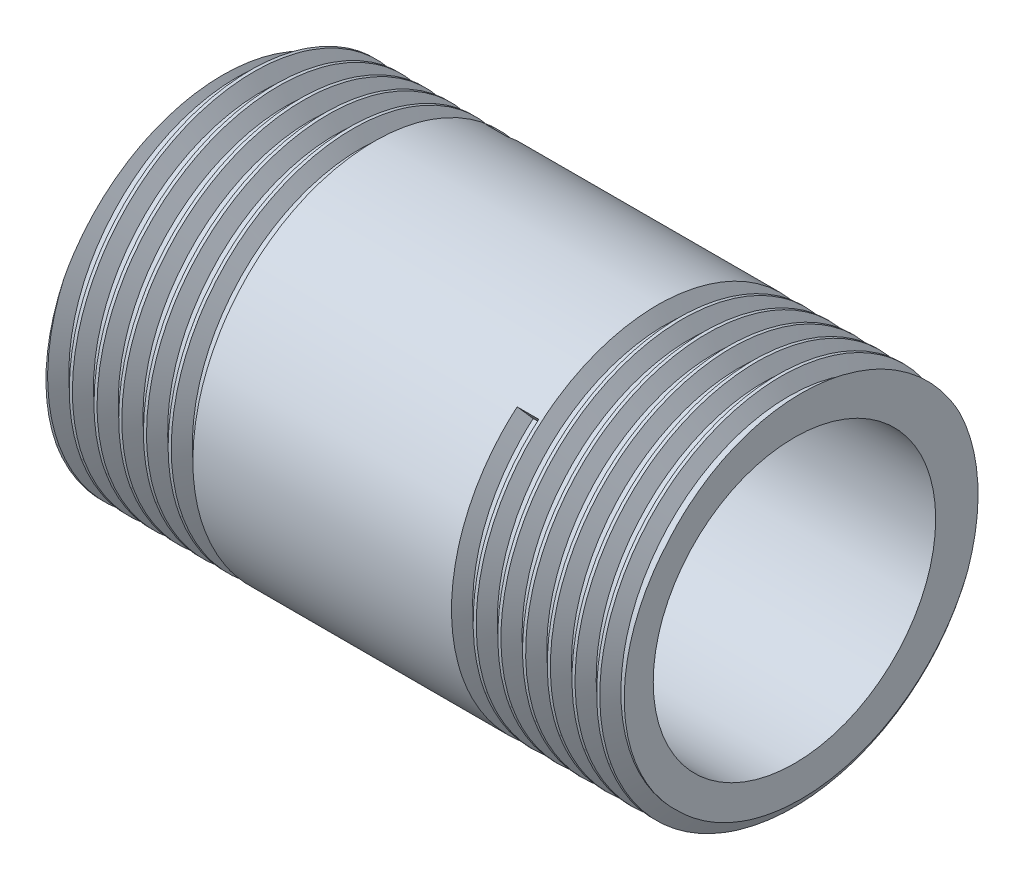
SolidWorks part; units mm, degrees
material "PVC rigide"
ref_plane "Plan de face" through (0, 0, 0) normal (0, 0, 1) x (1, 0, 0)
ref_plane "Plan de dessus" through (0, 0, 0) normal (0, 1, 0) x (1, 0, 0)
ref_plane "Plan de droite" through (0, 0, 0) normal (1, 0, 0) x (0, 0, -1)
sketch "Esquisse2" plane through (0, 0, 0) normal (1, 0, 0) x (0, 0, -1)
  circle A0 centre (0, 0) radius 13
  dimension "D1" = 26
extrude "Boss.-Extru.1" add sketch "Esquisse2" along normal mid plane 45
thread "Filetage1" pitch 1.75 method cut profile "Profil de filetage1" start angle 0, offset 0, length 12.5, pitch 1.75, diameter 26
ref_plane "Plan1" through (-22.5, 0, -13) normal (0, -1, 0) x (0, 0, -1)
sketch "Profil de filetage1" plane through (-22.5, 0, -13) normal (0, -1, 0) x (0, 0, -1)
  line L0 (0, 0) -> (0, 1.75) construction
  line L11 (0, 0) -> (0, 1.5312)
  line L12 (0, 1.5312) -> (-0.9472, 0.9844)
  line L13 (-0.9472, 0.9844) -> (-0.9472, 0.5469)
  line L15 (-0.9472, 0.5469) -> (0, 0)
  line L17 (-0.9472, 0.7656) -> (0, 0.7656) construction
  point P2 (0, 0)
  dimension "Pitch" = 1.75
  dimension "Profile_Angle" = 60
  dimension "Profile_Land" = 0.4375
  dimension "Profile_Height" = 0.9472
sketch "Esquisse5" plane through (-22.5, 0, 0) normal (-1, 0, 0) x (0, 0, 1)
  circle A0 centre (0, 0) radius 13.5
  dimension "D1" = 27
extrude "Enlèv. mat.-Extru.1" cut sketch "Esquisse5" against normal blind 2.5
thread "Filetage2" pitch 1.75 method cut profile "Profil de filetage2" start angle 0, offset 0, length 12.5, pitch 1.75, diameter 26
ref_plane "Plan2" through (22.5, 0, 13) normal (0, -1, 0) x (0, 0, 1)
sketch "Profil de filetage2" plane through (22.5, 0, 13) normal (0, -1, 0) x (0, 0, 1)
  line L0 (0, 0) -> (0, 1.75) construction
  line L11 (0, 0) -> (0, 1.5312)
  line L12 (0, 1.5312) -> (-0.9472, 0.9844)
  line L13 (-0.9472, 0.9844) -> (-0.9472, 0.5469)
  line L15 (-0.9472, 0.5469) -> (0, 0)
  line L17 (-0.9472, 0.7656) -> (0, 0.7656) construction
  point P2 (0, 0)
  dimension "Pitch" = 1.75
  dimension "Profile_Angle" = 60
  dimension "Profile_Land" = 0.4375
  dimension "Profile_Height" = 0.9472
sketch "Esquisse8" plane through (22.5, 0, 0) normal (1, 0, 0) x (0, 0, -1)
  circle A0 centre (0, 0) radius 13.5
  dimension "D1" = 27
extrude "Enlèv. mat.-Extru.2" cut sketch "Esquisse8" against normal blind 2.5
sketch "Esquisse9" plane through (-20, 0, 0) normal (-1, 0, 0) x (0, 0, 1)
  circle A0 centre (0, 0) radius 10
  dimension "D1" = 20
extrude "Enlèv. mat.-Extru.3" cut sketch "Esquisse9" against normal through all
